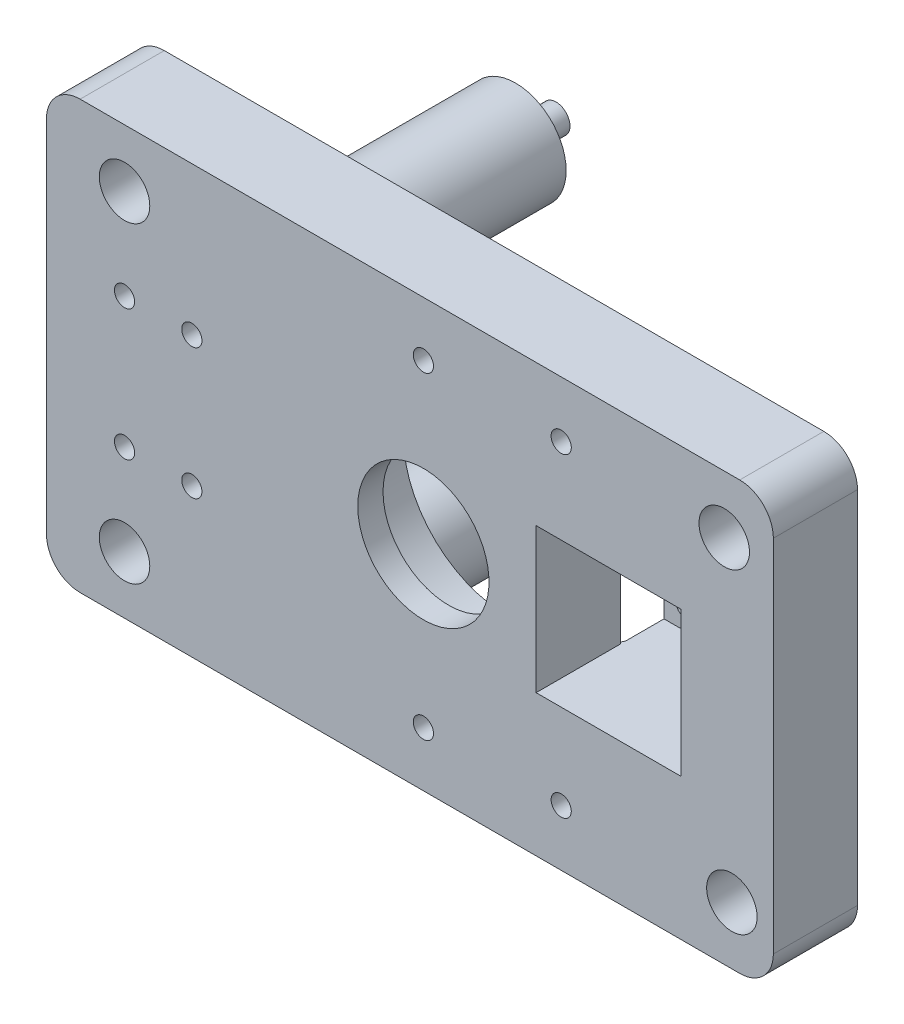
SolidWorks part; units mm, degrees
ref_plane "Front Plane" through (0, 0, 0) normal (0, 0, 1) x (1, 0, 0)
ref_plane "Top Plane" through (0, 0, 0) normal (0, 1, 0) x (1, 0, 0)
ref_plane "Right Plane" through (0, 0, 0) normal (1, 0, 0) x (0, 0, -1)
sketch "Sketch1" plane through (0, 0, 0) normal (0, 0, 1) x (1, 0, 0)
  line L1 (-108, 63.5) -> (108, 63.5)
  line L2 (-108, 63.5) -> (-108, -63.5)
  line L3 (-108, -63.5) -> (108, -63.5)
  line L4 (108, 63.5) -> (108, -63.5)
  line L5 (-108, 63.5) -> (108, -63.5) construction
  line L6 (-108, -63.5) -> (108, 63.5) construction
  point P0 (0, 0)
  dimension "D1" = 127
  dimension "D2" = 216
extrude "Boss-Extrude1" add sketch "Sketch1" along normal blind 25
fillet "Fillet1" radius 10 1 edges at (-108, 63.5, 12.5)
fillet "Fillet2" radius 10 3 edges at (-108, -63.5, 12.5) (108, 63.5, 12.5) (108, -63.5, 12.5)
sketch "Sketch9" plane through (0, 0, 0) normal (0, 0, -1) x (-1, 0, 0)
  line L0 (-98, 63.5) -> (98, 63.5) construction
  line L1 (-37.5, -21.5) -> (-80.5, -21.5)
  line L2 (-37.5, -21.5) -> (-37.5, 21.5)
  line L3 (-37.5, 21.5) -> (-80.5, 21.5)
  line L4 (-80.5, -21.5) -> (-80.5, 21.5)
  line L5 (-37.5, -21.5) -> (-80.5, 21.5) construction
  line L6 (-37.5, 21.5) -> (-80.5, -21.5) construction
  line L8 (108, 0) -> (-108, 0) construction
  line L9 (108, 53.5) -> (108, -53.5) construction
  line L10 (-108, -53.5) -> (-108, 53.5) construction
  circle A0 centre (-4, 0) radius 31
  point P2 (-59, 0)
  dimension "D6" = 62
  dimension "D1" = 27.5
  dimension "D2" = 55
  dimension "D3" = 43
  dimension "D4" = 43
  dimension "D5" = 63.5
extrude "Cut-Extrude4" cut sketch "Sketch9" against normal blind 17.5 contours A0
sketch "Sketch12" plane through (0, 0, 17.5) normal (0, 0, -1) x (-1, 0, 0)
  circle A0 centre (-4, 0) radius 19.5
  dimension "D1" = 39
extrude "Cut-Extrude5" cut sketch "Sketch12" against normal through all
extrude "Cut-Extrude6" cut sketch "Sketch9<4>" against normal through all contours L3 L4 L1 L2
sketch "Sketch9<4>" plane through (0, 0, 0) normal (0, 0, -1) x (-1, 0, 0) same geometry as "Sketch9"
sketch "Sketch13" plane through (0, 0, 0) normal (0, 0, -1) x (-1, 0, 0)
  line L1 (-37.5, -21.5) -> (-80.5, -21.5)
  line L2 (-37.5, -21.5) -> (-37.5, -25.5)
  line L3 (-37.5, -25.5) -> (-80.5, -25.5)
  line L4 (-80.5, -21.5) -> (-80.5, -25.5)
  dimension "D1" = 4
  dimension "D2" = 43
extrude "Boss-Extrude2" add sketch "Sketch13" along normal blind 17
ref_plane "Plane3" through (0, -21.5, 0) normal (0, 1, 0) x (1, 0, 0)
ref_plane "Plane4" through (0, 0, 0) normal (0, 0, -1) x (-1, 0, 0)
ref_plane "Plane6" through (80.5, 0, 0) normal (1, 0, 0) x (0, 0, -1)
sketch "Sketch16" plane through (80.5, 0, 0) normal (1, 0, 0) x (0, 0, -1)
  line L0 (17, -21.5) -> (0, -21.5) construction
  line L1 (17.0075, -21.5) -> (0.1109, -21.5)
  line L2 (17.0075, -21.5) -> (17.0075, -25.5)
  line L3 (17.0075, -25.5) -> (0.1109, -25.5)
  line L4 (0.1109, -21.5) -> (0.1109, -25.5)
  line L5 (17, -25.5) -> (0, -25.5) construction
fillet "Fillet4" radius 2 3 edges at (59, -25.5, 0) (37.5, -23.5, 0) (80.5, -23.5, 0)
sketch "Sketch17" plane through (0, -21.5, 0) normal (0, 1, 0) x (1, 0, 0)
  line L0 (80.5, 17.0075) -> (80.5, 0.1109) construction
  line L1 (37.5, 17) -> (80.5, 17)
  line L2 (37.5, 17) -> (37.5, 13)
  line L3 (37.5, 13) -> (80.5, 13)
  line L4 (80.5, 17) -> (80.5, 13)
  dimension "D1" = 4
extrude "Boss-Extrude5" add sketch "Sketch17" along normal blind 9
sketch "Sketch18" plane through (0, 0, 0) normal (0, 0, -1) x (-1, 0, 0)
  line L1 (-37.5, 21.5) -> (-80.5, 21.5)
  line L2 (-37.5, 21.5) -> (-37.5, 25.5)
  line L3 (-37.5, 25.5) -> (-80.5, 25.5)
  line L4 (-80.5, 21.5) -> (-80.5, 25.5)
  dimension "D1" = 43
  dimension "D2" = 4
extrude "Boss-Extrude6" add sketch "Sketch18" along normal blind 17
ref_plane "Plane7" through (0, 21.5, 0) normal (0, -1, 0) x (-1, 0, 0)
sketch "Sketch19" plane through (0, 21.5, 0) normal (0, -1, 0) x (-1, 0, 0)
  line L0 (-80.5, 17) -> (-80.5, 0) construction
  line L1 (-37.5, 17) -> (-80.5, 17)
  line L2 (-37.5, 17) -> (-37.5, 13)
  line L3 (-37.5, 13) -> (-80.5, 13)
  line L4 (-80.5, 17) -> (-80.5, 13)
  dimension "D1" = 4
extrude "Boss-Extrude7" add sketch "Sketch19" along normal blind 9
fillet "Fillet5" radius 2 3 edges at (37.5, 23.5, 0) (80.5, 23.5, 0) (59, 25.5, 0)
ref_plane "Plane8" through (0, 0, -17) normal (0, 0, -1) x (-1, 0, 0)
sketch "Sketch20" plane through (0, 0, -17) normal (0, 0, -1) x (-1, 0, 0)
  line L0 (-37.5, -25.5) -> (-37.5, -12.5) construction
  line L2 (-80.5, -21.5) -> (-37.5, -21.5)
  line L3 (-80.5, -12.5) -> (-80.5, -25.5) construction
  line L4 (-80.5, -12.5) -> (-37.5, -12.5) construction
  circle A0 centre (-43.15, -16) radius 1.85
  circle A1 centre (-74.85, -16) radius 1.85
  dimension "D3" = 5.5
  dimension "D4" = 3.7
  dimension "D5" = 5.65
  dimension "D6" = 3.7
  dimension "D1" = 5.65
  dimension "D2" = 9
extrude "Cut-Extrude7" cut sketch "Sketch20" against normal blind 9 contours A1 | A0
ref_plane "Plane9" through (0, 0, -17) normal (0, 0, -1) x (-1, 0, 0)
sketch "Sketch23" plane through (0, 0, -17) normal (0, 0, -1) x (-1, 0, 0)
  line L0 (-37.5, 21.5) -> (-80.5, 21.5)
  line L1 (-37.5, 12.5) -> (-37.5, 25.5) construction
  line L2 (-80.5, 25.5) -> (-80.5, 12.5) construction
  line L3 (-37.5, 12.5) -> (-80.5, 12.5) construction
  circle A0 centre (-43.15, 15.85) radius 1.85
  circle A1 centre (-74.85, 16) radius 1.85
  dimension "D4" = 3.7
  dimension "D5" = 3.7
  dimension "D6" = 5.65
  dimension "D7" = 5.65
  dimension "D1" = 9
  dimension "D2" = 5.5
  dimension "D3" = 5.65
extrude "Cut-Extrude8" cut sketch "Sketch23" against normal blind 9 contours A0 | A1
ref_plane "Plane10" through (0, 0, 0) normal (0, 0, -1) x (-1, 0, 0)
sketch "Sketch25" plane through (0, 0, 0) normal (0, 0, -1) x (-1, 0, 0)
  line L0 (5.8491, 5.5555) -> (-31.0008, -15.2301)
  line L1 (-4, -31) -> (-4, 31)
  line L2 (98, -63.5) -> (-98, -63.5) construction
  line L3 (-98, 63.5) -> (98, 63.5) construction
  circle A0 centre (5.8491, 5.5555) radius 0.0422
  circle A1 centre (-4, 0) radius 31 construction
  circle A2 centre (42.4241, -43.5) radius 15
  circle A3 centre (42.4241, 43.5) radius 15
  point P8 (-12.5759, -4.8373)
  dimension "D4" = 20
  dimension "D5" = 30
  dimension "D6" = 30
  dimension "D1" = 55
  dimension "D2" = 55
  dimension "D3" = 20
extrude "Boss-Extrude9" add sketch "Sketch25" along normal blind 48.84 contours A3 | A2
ref_plane "Plane11" through (0, 0, -48.84) normal (0, 0, -1) x (-1, 0, 0)
sketch "Sketch26" plane through (0, 0, -48.84) normal (0, 0, -1) x (-1, 0, 0)
  circle A0 centre (42.4241, -43.5) radius 4.15
  dimension "D1" = 8.3
extrude "Boss-Extrude10" add sketch "Sketch26" along normal blind 12
ref_plane "Plane12" through (0, 0, -48.84) normal (0, 0, -1) x (-1, 0, 0)
sketch "Sketch27" plane through (0, 0, -48.84) normal (0, 0, -1) x (-1, 0, 0)
  circle A0 centre (42.4241, 43.5) radius 4.15
  dimension "D1" = 8.3
extrude "Boss-Extrude11" add sketch "Sketch27" along normal blind 12
fillet "Fillet9" radius 2 1 edges at (-27.4241, -43.5, 0)
fillet "Fillet10" radius 2 1 edges at (-27.4241, 43.5, 0)
ref_plane "Plane13" through (0, 0, 25) normal (0, 0, 1) x (1, 0, 0)
sketch "Sketch28" plane through (0, 0, 25) normal (0, 0, 1) x (1, 0, 0)
  line L0 (98, 63.5) -> (-98, 63.5) construction
  line L3 (-98, -63.5) -> (98, -63.5) construction
  circle A0 centre (-84.8117, 46.37) radius 7.5
  circle A1 centre (-84.8117, -46.37) radius 7.5
  circle A2 centre (95.674, -46.3698) radius 7.5
  circle A3 centre (93.3991, 46.37) radius 7.5
  dimension "D2" = 15
  dimension "D3" = 17.13
  dimension "D4" = 15
  dimension "D5" = 17.13
  dimension "D6" = 15
  dimension "D7" = 15
  dimension "D1" = 17.13
extrude "Cut-Extrude9" cut sketch "Sketch28" against normal through all
ref_plane "Plane14" through (0, 0, 0) normal (0, 0, -1) x (-1, 0, 0)
sketch "Sketch29" plane through (0, 0, 0) normal (0, 0, -1) x (-1, 0, 0)
  line L0 (-108, 0) -> (108, 0) construction
  line L1 (-108, -53.5) -> (-108, 53.5) construction
  line L2 (108, 53.5) -> (108, -53.5) construction
  line L3 (-4, -31) -> (-4, -63.5) construction
  line L4 (-4, 47.25) -> (-85.8991, 46.37) construction
  line L5 (98, -63.5) -> (-98, -63.5) construction
  line L6 (84.8117, -38.87) -> (84.8117, 0) construction
  line L7 (-4, 31) -> (-4, 63.5) construction
  line L8 (-98, 63.5) -> (98, 63.5) construction
  line L9 (84.8117, 19.435) -> (64.8117, 19.435) construction
  circle A3 centre (-44.9495, 46.81) radius 3
  circle A4 centre (-93.3991, 46.37) radius 7.5 construction
  circle A5 centre (-4, 0) radius 31 construction
  circle A6 centre (-4, 0) radius 31 construction
  circle A7 centre (-4, 47.25) radius 3
  circle A9 centre (-4, -47.25) radius 3
  circle A10 centre (-44.9495, -46.81) radius 3
  circle A11 centre (84.8117, -19.435) radius 3
  circle A12 centre (84.8117, -46.37) radius 7.5 construction
  circle A13 centre (84.8117, 19.435) radius 3
  circle A14 centre (64.8117, 19.435) radius 3
  circle A15 centre (64.8117, -19.435) radius 3
  point P33 (-44.9495, 46.81)
  point P39 (84.8117, -19.435)
  dimension "D1" = 6
  dimension "D2" = 20
extrude "Cut-Extrude11" cut sketch "Sketch29" against normal through all contours A7 | A11 | A9 | A14 | A13 | A15 | A3 | A10
ref_plane "Plane15" through (0, 0, 5) normal (0, 0, -1) x (-1, 0, 0)
ref_plane "Plane16" through (0, 0, 10) normal (0, 0, -1) x (-1, 0, 0)
ref_plane "Plane17" through (0, 0, 17.5) normal (0, 0, -1) x (-1, 0, 0)
